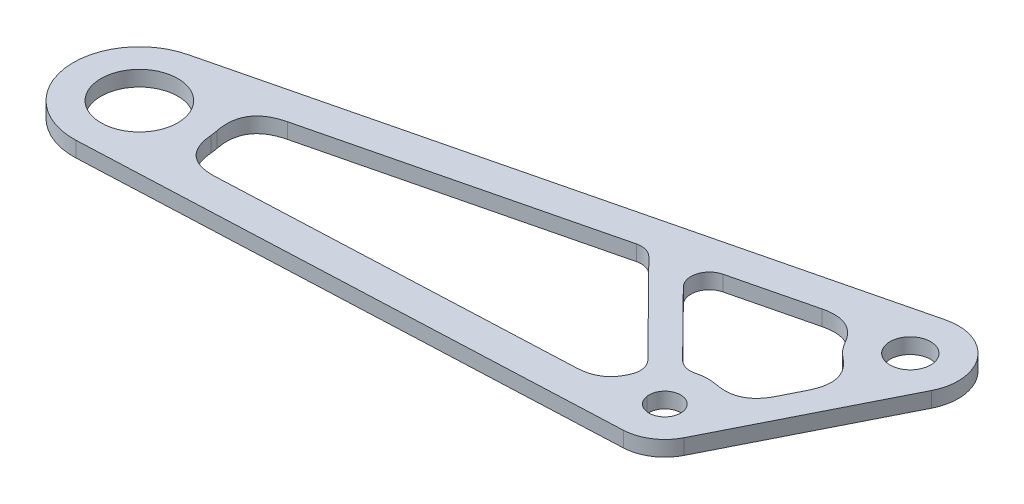
SolidWorks part; units mm, degrees
material "6061-T6 (SS)"
ref_plane "Front Plane" through (0, 0, 0) normal (0, 0, 1) x (1, 0, 0)
ref_plane "Top Plane" through (0, 0, 0) normal (0, 1, 0) x (1, 0, 0)
ref_plane "Right Plane" through (0, 0, 0) normal (1, 0, 0) x (0, 0, -1)
sketch "Sketch1" plane through (0, 0, 0) normal (0, 1, 0) x (1, 0, 0)
  line L0 (0, 0) -> (124.8778, 34.4406) construction
  line L1 (124.8778, 34.4406) -> (108.585, 0) construction
  line L2 (108.585, 0) -> (0, 0) construction
  line L3 (-3.2476, 13.2606) -> (122.5214, 44.0623)
  line L5 (116.6057, -4.036) -> (133.7266, 29.9879)
  line L6 (108.585, 0) -> (109.8191, -8.8937) construction
  line L7 (-1.8881, 7.7097) -> (123.8808, 38.5113)
  line L8 (111.5006, -1.4671) -> (128.6215, 32.5568)
  line L9 (0.3416, -7.9301) -> (108.7255, -3.2609)
  line L10 (108.585, 0) -> (80.9067, 27.9867) construction
  line L11 (108.585, 0) -> (108.585, 29.9472) construction
  line L12 (74.1927, 26.3424) -> (50.6623, -5.7623) construction
  line L13 (78.0308, 27.2823) -> (53.9142, -5.6222)
  line L14 (70.3546, 25.4024) -> (47.4105, -5.9024)
  line L15 (78.0308, 27.2823) -> (100.7231, 4.3373)
  line L16 (83.7825, 28.691) -> (104.3351, 7.9094)
  line L17 (62.4275, 10.29) -> (60.3789, 11.7916) construction
  line L18 (62.4275, 10.29) -> (64.4762, 8.7885) construction
  line L19 (94.7458, 13.9933) -> (92.9399, 12.2073) construction
  line L20 (94.7458, 13.9933) -> (96.5518, 15.7794) construction
  line L21 (114.3014, 6.9241) -> (123.2323, 24.6722)
  line L22 (0.5876, -13.6398) -> (108.9715, -8.9706)
  line L23 (9.9856, 9.3101) -> (114.9891, 35.0261)
  line L24 (12.1896, -6.1485) -> (99.9242, -2.3689)
  circle A0 centre (0, 0) radius 7.9375
  circle A1 centre (124.8778, 34.4406) radius 4.191
  circle A2 centre (108.585, 0) radius 3.2639
  circle A3 centre (0, 0) radius 13.6525
  circle A4 centre (108.585, 0) radius 8.9789
  circle A5 centre (124.8778, 34.4406) radius 9.906
  arc A6 (-3.2476, 13.2606) -> (6.5337, -11.9876) centre (0, 0) ccw
  arc A7 (116.6057, -4.036) -> (108.585, -8.9789) centre (108.585, 0) cw
  arc A8 (122.5214, 44.0623) -> (133.7266, 29.9879) centre (124.8778, 34.4406) cw
  dimension "D4" = 15.875
  dimension "D5" = 6.5278
  dimension "D6" = 8.382
  dimension "D7" = 5.715
  dimension "D8" = 5.715
  dimension "D9" = 5.715
  dimension "D1" = 129.54
  dimension "D2" = 38.1
  dimension "D3" = 108.585
  dimension "D10" = 97.9
  dimension "D11" = 70
  dimension "D12" = 40
  dimension "D13" = 5.08
  dimension "D14" = 1.27
  dimension "D15" = 1.27
  dimension "D16" = 1.27
extrude "Boss-Extrude4" add sketch "Sketch1" against normal blind 3.175 contours A5 L7 A1 L8 | A5 L3 A3 L7 | A3 L9 A0 L7 | L9 A3 L7 A0 | A3 L23 L14 L7 | A3 L9 L14 L24 | A4 L9 A3 L22 | A4 L24 L13 L9 | L24 L14 L9 L13 | A4 L16 L23 L15 | L14 L23 L13 L7 | L15 L23 L16 L7 | A5 L7 L16 L23 | L13 L23 L15 | A5 L8 A4 L5 | L7 A5 L8 A1 | A4 L8 A2 L9 | L8 A4 L9 A2 region at (3.0925, 0, -12.9166) region at (60.9421, 0, -26.1046) region at (130.8206, 0, -42.0146) region at (55.5019, 0, 8.4889) region at (9.0069, 0, -1.2841) region at (39.615, 0, -17.2244) region at (99.6799, 0, -31.9349) region at (120.3421, 0, -30.8296) region at (110.8898, 0, 3.5657) region at (73.6087, 0, -25.5456) region at (122.752, 0, -13.9922) region at (81.4272, 0, -27.4604) region at (29.8616, 0, 6.0222) region at (77.9885, 0, -26.4003) region at (92.1113, 0, -16.5941) region at (106.4195, 0, -3.3502) region at (77.2616, 0, 3.984) region at (51.1433, 0, 5.106)
ref_plane "Plane1" through (108.585, 0, 0) normal (0.1374, 0, 0.9905) x (0.9905, 0, -0.1374)
split line "Split Line1"
sketch "Sketch2" [suppressed] plane through (0, -3.175, 0) normal (0, -1, 0) x (1, 0, 0)
  line L1 (69.4473, -23.6659) -> (60.7288, -1.2641)
  line L2 (62.8949, 2.1892) -> (101.6127, 5.2609)
  line L3 (101.2476, -37.8411) -> (79.7056, -31.0891)
  line L4 (79.2148, -26.4545) -> (98.3531, -15.6299)
  line L5 (59.9072, -25.992) -> (7.538, -8.592)
  line L6 (63.0965, -22.7173) -> (54.4829, 1.0899)
  line L7 (51.7805, 2.7463) -> (11.1946, -2.3078)
  line L8 (73.1912, -24.8791) -> (102.155, -6.1958)
  line L9 (104.5239, -35.0732) -> (102.1201, -17.4966)
  circle A0 centre (111.76, 0) radius 11.43 construction
  circle A3 centre (0, 0) radius 11.43 construction
  arc A4 (11.1946, -2.3078) -> (7.538, -8.592) centre (0, 0) cw
  arc A5 (101.6127, 5.2609) -> (102.155, -6.1958) centre (111.76, 0) ccw
  arc A6 (101.2476, -37.8411) -> (104.5239, -35.0732) centre (102.0073, -35.4173) ccw
  arc A7 (98.3531, -15.6299) -> (102.1201, -17.4966) centre (99.6035, -17.8407) cw
  arc A8 (69.4473, -23.6659) -> (73.1912, -24.8791) centre (71.8144, -22.7446) ccw
  arc A9 (60.7288, -1.2641) -> (62.8949, 2.1892) centre (63.0958, -0.3428) cw
  arc A10 (63.0965, -22.7173) -> (59.9072, -25.992) centre (60.7081, -23.5815) cw
  arc A11 (54.4829, 1.0899) -> (51.7805, 2.7463) centre (52.0944, 0.2257) ccw
  arc A12 (79.2148, -26.4545) -> (79.7056, -31.0891) centre (80.4653, -28.6654) ccw
  dimension "D1" = 2.54
  dimension "D2" = 2.54
  dimension "D3" = 2.54
  dimension "D4" = 2.54
  dimension "D5" = 2.54
  dimension "D6" = 2.54
  dimension "D7" = 2.54
extrude "Cut-Extrude2" [suppressed] cut sketch "Sketch2" against normal through all
fillet "Fillet1" radius 7.62 6 edges at (115.2605, -1.5875, -6.0049) (124.5869, -1.5875, -24.5389) (114.9891, -1.5875, -35.0261) (9.9856, -1.5875, -9.3101) (99.9242, -1.5875, 2.3689) (12.1896, -1.5875, 6.1485) conic rho 0.5
fillet "Fillet2" radius 3.81 4 edges at (104.3351, -1.5875, -7.9094) (100.7231, -1.5875, -4.3373) (84.8235, -1.5875, -27.6384) (79.0718, -1.5875, -26.2298)
fillet "Fillet3" [suppressed] radius 2.54
equation "\"x\"= .05"
